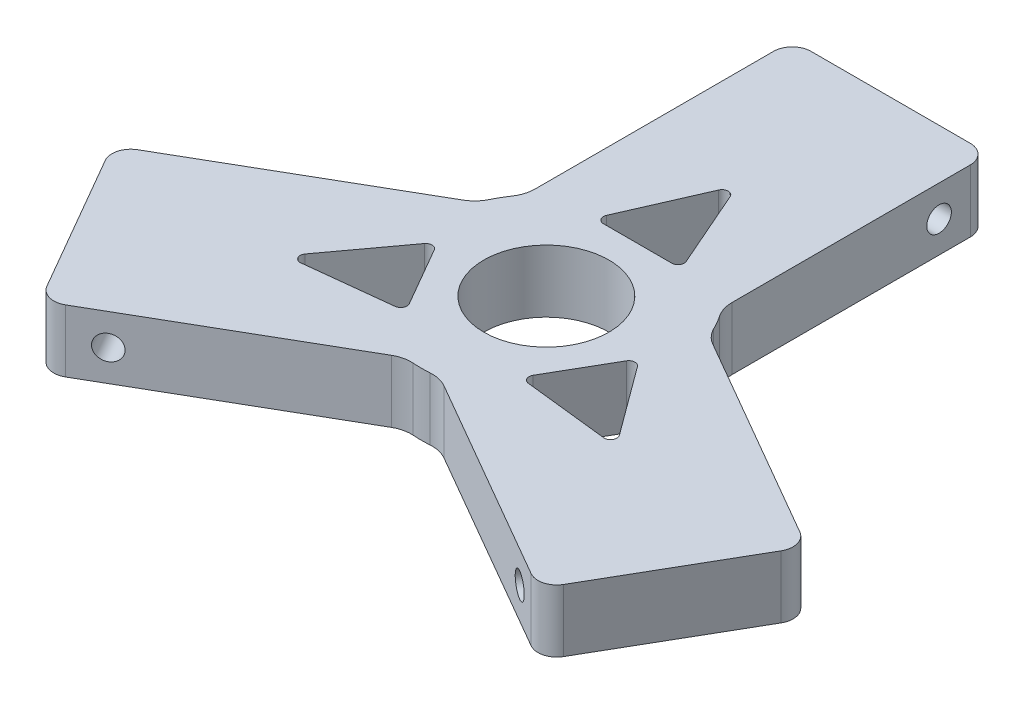
SolidWorks part; units mm, degrees
ref_plane "Front Plane" through (0, 0, 0) normal (0, 0, 1) x (1, 0, 0)
ref_plane "Top Plane" through (0, 0, 0) normal (0, 1, 0) x (1, 0, 0)
ref_plane "Right Plane" through (0, 0, 0) normal (1, 0, 0) x (0, 0, -1)
sketch "Sketch1" plane through (0, 0, 0) normal (0, 1, 0) x (1, 0, 0)
  line L0 (0, 35) -> (10, 35)
  line L1 (0, 35) -> (-10, 35)
  line L2 (0, 35) -> (0, 0) construction
  line L3 (0, 0) -> (-30.3109, -17.5) construction
  line L4 (0, 0) -> (30.3109, -17.5) construction
  line L5 (-10, 35) -> (-10, 7.8288)
  line L6 (10, 35) -> (10, 7.8288)
  line L7 (30.3109, -17.5) -> (35.3109, -8.8397)
  line L8 (30.3109, -17.5) -> (25.3109, -26.1603)
  line L9 (-30.3109, -17.5) -> (-35.3109, -8.8397)
  line L10 (-30.3109, -17.5) -> (-25.3109, -26.1603)
  line L11 (-35.3109, -8.8397) -> (-11.7799, 4.7459)
  line L12 (-25.3109, -26.1603) -> (-1.7799, -12.5747)
  line L13 (25.3109, -26.1603) -> (1.7799, -12.5747)
  line L14 (35.3109, -8.8397) -> (11.7749, 4.7582)
  circle A0 centre (0, 0) radius 35 construction
  arc A1 (-10, 7.8288) -> (-11.7799, 4.7459) centre (0, 0) ccw construction
  arc A2 (-10, 7.8288) -> (-11.7799, 4.7459) centre (0, 0) ccw
  arc A3 (11.7749, 4.7582) -> (10, 7.8288) centre (0, 0) ccw construction
  arc A4 (11.7749, 4.7582) -> (10, 7.8288) centre (0, 0) ccw
  arc A5 (-1.7799, -12.5747) -> (1.7799, -12.5747) centre (0, 0) ccw construction
  arc A6 (-1.7799, -12.5747) -> (1.7799, -12.5747) centre (0, 0) ccw
  dimension "D1" = 70
  dimension "D6" = 25.4
  dimension "D2" = 10
  dimension "D3" = 20
  dimension "D4" = 120
  dimension "D5" = 120
  dimension "D7" = 90
  dimension "D8" = 10
  dimension "D9" = 20
  dimension "D10" = 90
  dimension "D11" = 10
  dimension "D12" = 20
  dimension "D13" = 90
extrude "Boss-Extrude1" add sketch "Sketch1" along normal blind 6.35
hole_wizard "M3x0.5 Tapped Hole2" positions "Sketch4" profile "Sketch5" tap size "M3x0.5" standard "ANSI Metric" end condition through all
sketch "Sketch4" plane through (10, 0, 0) normal (1, 0, 0) x (0, 0, -1)
  line L0 (35, 6.35) -> (35, 0) construction
  point P0 (29.92, 3.175)
  point P5 (35, 3.175)
  dimension "D1" = 5.08
sketch "Sketch5" plane through (10, 3.175, -29.92) normal (0, 1, 0) x (0, 0, -1)
  line L0 (0, 0) -> (0, 45.3109)
  line L1 (0, 45.3109) -> (1.25, 45.3109)
  line L2 (1.25, 45.3109) -> (1.25, 0)
  line L5 (1.25, 0) -> (0, 0)
  line L11 (0, -6.35) -> (0, 107.95) construction
  dimension "Thru Tap Drill Dia." = 2.5
  dimension "Thru Tap Drill Depth" = 45.3109
cosmetic thread "Hole Thread2" parameters "D2"=3
hole_wizard "M3x0.5 Tapped Hole3" positions "Sketch6" profile "Sketch7" tap size "M3x0.5" standard "ANSI Metric" end condition through all
sketch "Sketch6" plane through (-5, 0, -8.6603) normal (-0.5, 0, -0.866) x (-0.866, 0, 0.5)
  line L0 (35, 6.35) -> (35, 0) construction
  point P0 (29.92, 3.175)
  point P5 (35, 3.175)
  dimension "D1" = 5.08
sketch "Sketch7" plane through (-30.9115, 3.175, 6.2997) normal (0, 1, 0) x (-0.866, 0, 0.5)
  line L0 (0, 0) -> (0, 50.3109)
  line L1 (0, 50.3109) -> (1.25, 50.3109)
  line L2 (1.25, 50.3109) -> (1.25, 0)
  line L5 (1.25, 0) -> (0, 0)
  line L11 (0, -6.35) -> (0, 107.95) construction
  dimension "Thru Tap Drill Dia." = 2.5
  dimension "Thru Tap Drill Depth" = 50.3109
cosmetic thread "Hole Thread3" parameters "D2"=3
hole_wizard "M3x0.5 Tapped Hole4" positions "Sketch8" profile "Sketch9" tap size "M3x0.5" standard "ANSI Metric" end condition through all
sketch "Sketch8" plane through (-5, 0, 8.6603) normal (-0.5, 0, 0.866) x (0.866, 0, 0.5)
  line L0 (35, 6.35) -> (35, 0) construction
  point P0 (29.92, 3.175)
  point P5 (35, 3.175)
  dimension "D1" = 5.08
sketch "Sketch9" plane through (20.9115, 3.175, 23.6203) normal (0, 1, 0) x (0.866, 0, 0.5)
  line L0 (0, 0) -> (0, 57.9663)
  line L1 (0, 57.9663) -> (1.25, 57.9663)
  line L2 (1.25, 57.9663) -> (1.25, 0)
  line L5 (1.25, 0) -> (0, 0)
  line L11 (0, -6.35) -> (0, 107.95) construction
  dimension "Thru Tap Drill Dia." = 2.5
  dimension "Thru Tap Drill Depth" = 57.9663
cosmetic thread "Hole Thread4" parameters "D2"=3
fillet "Fillet1" radius 3.175 6 edges at (-11.7799, 3.175, -4.7459) (-10, 3.175, -7.8288) (-1.7799, 3.175, 12.5747) (1.7799, 3.175, 12.5747) (11.7749, 3.175, -4.7582) (10, 3.175, -7.8288)
sketch "Sketch10" plane through (0, 6.35, 0) normal (0, 1, 0) x (1, 0, 0)
  circle A0 centre (0, 0) radius 6.36
  dimension "D1" = 12.72
extrude "Cut-Extrude1" cut sketch "Sketch10" against normal through all
sketch "Sketch11" plane through (0, 6.35, 0) normal (0, 1, 0) x (1, 0, 0)
  line L0 (0, 19.4327) -> (-4.445, 9.2727)
  line L1 (-4.445, 9.2727) -> (4.445, 9.2727)
  line L2 (4.445, 9.2727) -> (0, 19.4327)
  line L3 (10, 35) -> (-10, 35) construction
  point P2 (0, 9.2727)
  point P7 (0, 35)
  dimension "D1" = 8.89
  dimension "D2" = 10.16
extrude "Cut-Extrude2" cut sketch "Sketch11" against normal through all
fillet "Fillet2" radius 0.635 3 edges at (-4.445, 3.175, -9.2727) (4.445, 3.175, -9.2727) (0, 3.175, -19.4327)
pattern_circular "CirPattern1" count 2 over 120 about axis through (0, 6.35, 0) along (0, 1, 0) of "Fillet2", "Cut-Extrude2"
pattern_circular "CirPattern5" count 2 over 240 about axis through (0, 6.35, 0) along (0, 1, 0) of "Cut-Extrude2", "Fillet2"
fillet "Fillet3" radius 1.905 6 edges at (25.3109, 3.175, 26.1603) (35.3109, 3.175, 8.8397) (10, 3.175, -35) (-10, 3.175, -35) (-35.3109, 3.175, 8.8397) (-25.3109, 3.175, 26.1603)
